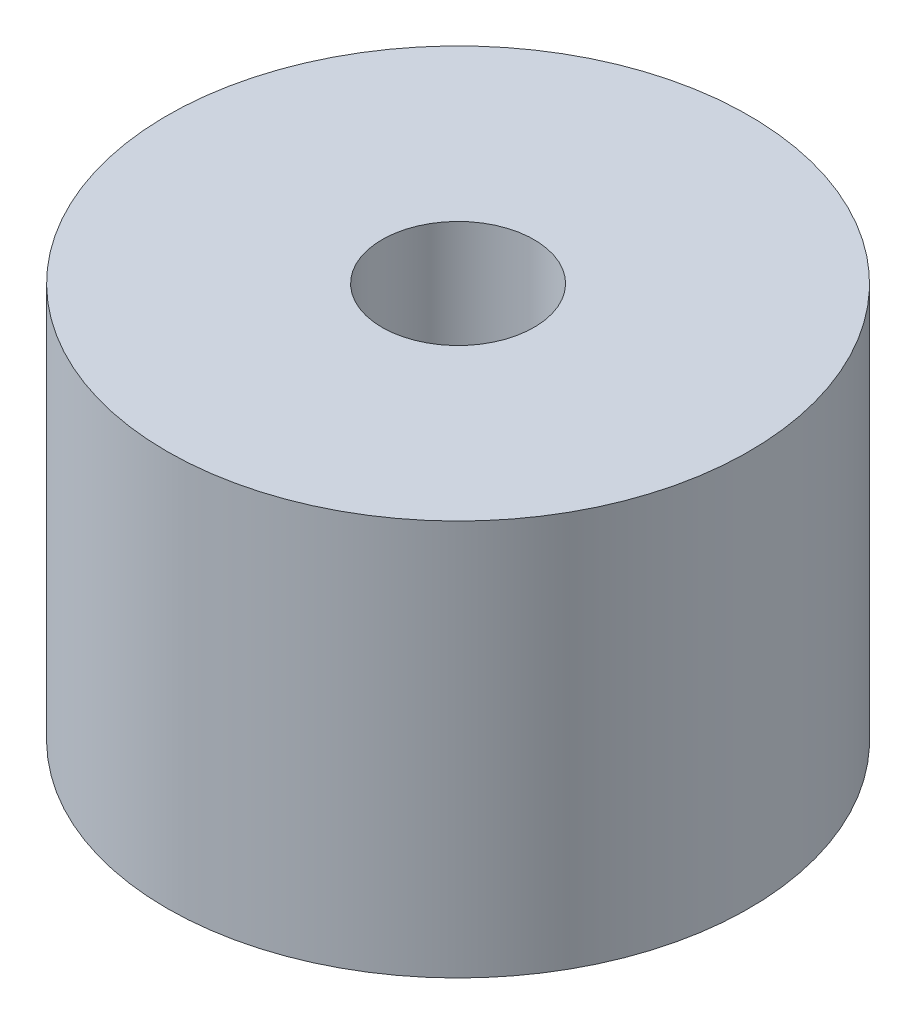
SolidWorks part; units mm, degrees
material "PTFE (general)"
ref_plane "Front Plane" through (0, 0, 0) normal (0, 0, 1) x (1, 0, 0)
ref_plane "Top Plane" through (0, 0, 0) normal (0, 1, 0) x (1, 0, 0)
ref_plane "Right Plane" through (0, 0, 0) normal (1, 0, 0) x (0, 0, -1)
sketch "Sketch1" plane through (0, 0, 0) normal (0, 1, 0) x (1, 0, 0)
  circle A0 centre (0, 0) radius 9.525
  dimension "D1" = 19.05
extrude "Boss-Extrude1" add sketch "Sketch1" along normal blind 12.954
hole_wizard "#10 Clearance Hole1" positions "Sketch2" profile "Sketch3" hole size "#10" standard "ANSI Inch" end condition through all
sketch "Sketch2" plane through (0, 12.954, 0) normal (0, 1, 0) x (1, 0, 0)
  point P0 (0, 0)
sketch "Sketch3" plane through (0, 12.954, 0) normal (1, 0, 0) x (0, 0, 1)
  line L0 (0, 0) -> (0, 12.954)
  line L1 (0, 12.954) -> (2.4892, 12.954)
  line L2 (2.4892, 12.954) -> (2.4892, 0)
  line L5 (2.4892, 0) -> (0, 0)
  line L11 (0, -6.35) -> (0, 107.95) construction
  dimension "Thru Hole Dia." = 4.9784
  dimension "Thru Hole Depth" = 12.954
